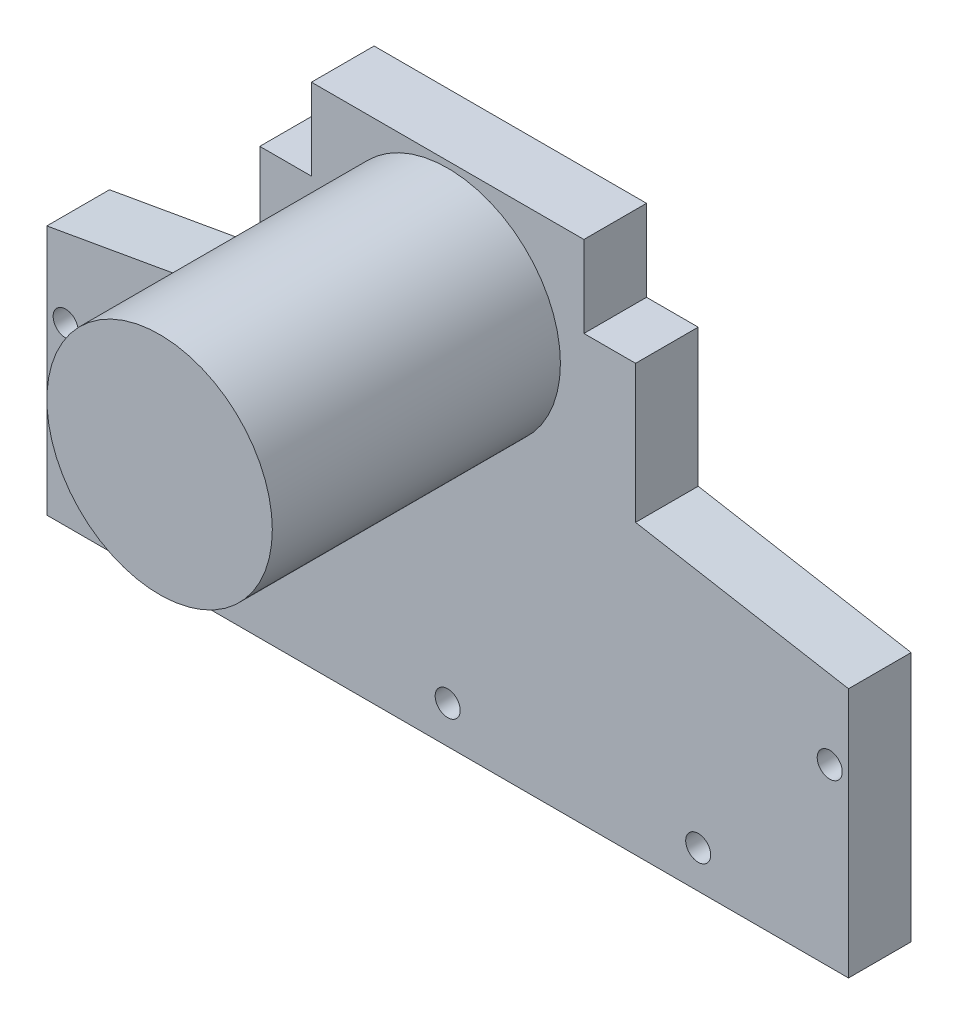
SolidWorks part; units mm, degrees
material "Nickel"
ref_plane "Front Plane" through (0, 0, 0) normal (0, 0, 1) x (1, 0, 0)
ref_plane "Top Plane" through (0, 0, 0) normal (0, 1, 0) x (1, 0, 0)
ref_plane "Right Plane" through (0, 0, 0) normal (1, 0, 0) x (0, 0, -1)
sketch "Sketch1" plane through (0, 0, 0) normal (0, 0, 1) x (1, 0, 0)
  line L0 (-32, 0) -> (32, 0)
  line L1 (-1015.4659, 23) -> (48984.5341, 23) construction
  line L2 (-15, 23) -> (15, 23)
  line L3 (-32, 0) -> (-32, 20)
  line L4 (-32, 20) -> (-15, 23)
  line L5 (32, 0) -> (32, 20)
  line L6 (32, 20) -> (15, 23)
  line L7 (-15, 23) -> (-15, 34)
  line L8 (-15, 34) -> (15, 34)
  line L9 (15, 34) -> (15, 23)
  line L10 (-1006.9308, 40.5) -> (48993.0692, 40.5) construction
  line L11 (-10.875, 40.5) -> (10.875, 40.5)
  line L12 (-10.875, 40.5) -> (-10.875, 34)
  line L13 (10.875, 40.5) -> (10.875, 34)
  line L14 (0, 34) -> (0, 40.5) construction
  dimension "D1" = 64
  dimension "D2" = 23
  dimension "D3" = 30
  dimension "D4" = 20
  dimension "D5" = 11
  dimension "D6" = 6.5
  dimension "D7" = 21.75
extrude "Boss-Extrude1" add sketch "Sketch1" along normal blind 5 contours L5 L6 L2 L4 L3 L0 | L9 L8 L7 L2 | L13 L11 L12 L8 region at (0, 11.1232, 0) region at (0, 28.5, 0) region at (0, 37.25, 0)
sketch "Sketch2" plane through (0, 0, 5) normal (0, 0, 1) x (1, 0, 0)
  line L0 (-1024.4669, 3) -> (48975.5331, 3) construction
  line L1 (-32, 0) -> (32, 0) construction
  line L2 (-20, 3) -> (20, 3)
  line L3 (-32, 0) -> (-32, 20) construction
  line L4 (0, -997) -> (0, 49003) construction
  circle A0 centre (-20, 3) radius 1
  circle A1 centre (20, 3) radius 1
  circle A2 centre (0, 3) radius 1
  circle A3 centre (-30.5, 14) radius 1
  circle A4 centre (30.5, 14) radius 1
  dimension "D3" = 2
  dimension "D1" = 40
  dimension "D2" = 3
  dimension "D5" = 14
  dimension "D6" = 1.5
extrude "Cut-Extrude1" cut sketch "Sketch2" against normal blind 5 contours A3 | A1 | A0 | A2 | A4 region at (20, 3.9717, 5) region at (-30.5, 14, 5)
sketch "Sketch3" plane through (0, 0, 5) normal (0, 0, 1) x (1, 0, 0)
  line L0 (0, 40.5) -> (0, 0) construction
  line L1 (-10.875, 40.5) -> (10.875, 40.5) construction
  line L2 (-32, 0) -> (32, 0) construction
  line L4 (-8.5, 39.5) -> (8.5, 39.5)
  line L5 (-8.5, 39.5) -> (-8.5, 22.5)
  line L6 (-8.5, 22.5) -> (8.5, 22.5)
  line L7 (8.5, 39.5) -> (8.5, 22.5)
  circle A0 centre (0, 31) radius 9
  circle A1 centre (0, 31) radius 8.5
  dimension "D1" = 18
  dimension "D2" = 17
  dimension "D3" = 17
  dimension "D4" = 1
extrude "Boss-Extrude2" add sketch "Sketch3" along normal blind 23 contours A0
sketch "Sketch4" plane through (0, 0, 28) normal (0, 0, 1) x (1, 0, 0)
  circle A0 centre (0, 31) radius 9
